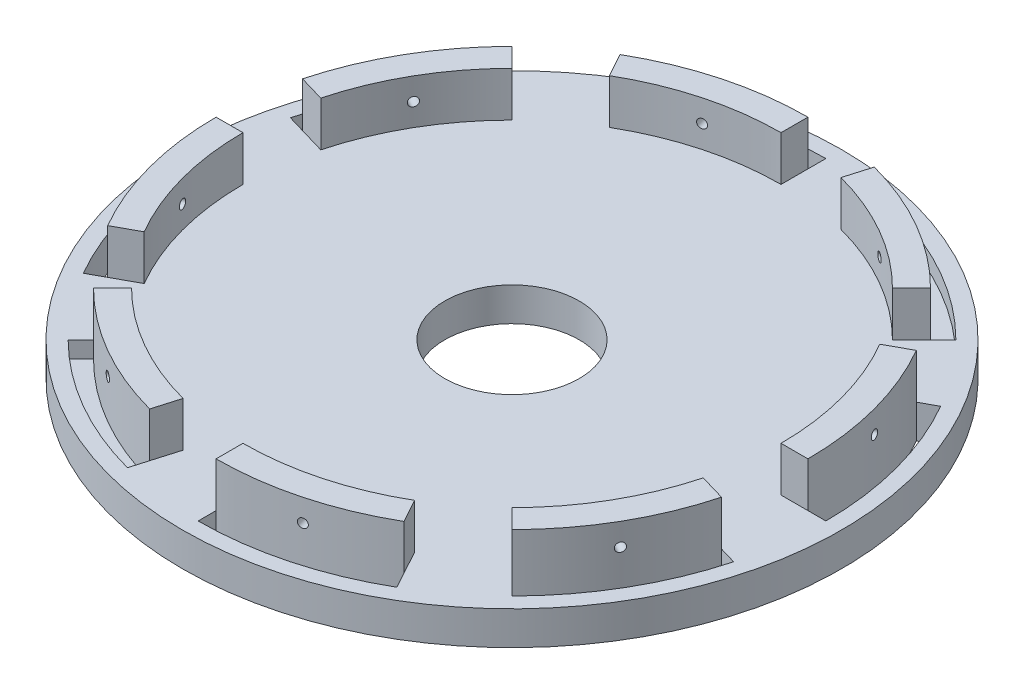
SolidWorks part; units mm, degrees
material "6061-T6 (SS)"
ref_plane "Front Plane" through (0, 0, 0) normal (0, 0, 1) x (1, 0, 0)
ref_plane "Top Plane" through (0, 0, 0) normal (0, 1, 0) x (1, 0, 0)
ref_plane "Right Plane" through (0, 0, 0) normal (1, 0, 0) x (0, 0, -1)
sketch "Sketch1" plane through (0, 0, 0) normal (0, 1, 0) x (1, 0, 0)
  circle A0 centre (0, 0) radius 93.345
  dimension "D1" = 186.69
extrude "Base" add sketch "Sketch1" along normal blind 4.7625 and the other way blind 4.7625
sketch "Sketch2" plane through (0, 4.7625, 0) normal (0, 1, 0) x (1, 0, 0)
  line L0 (0, 0) -> (0, 93.345) construction
  line L1 (-55, 0) -> (55, 0) construction
  line L2 (0, 88.9) -> (0, 83.82)
  line L3 (-41.9567, 72.5633) -> (-44.3929, 77.0226)
  line L4 (0, 0) -> (0, 93.345) construction
  arc A0 (-41.9567, 72.5633) -> (0, 83.82) centre (0, 0) cw
  arc A1 (-44.3929, 77.0226) -> (0, 88.9) centre (0, 0) cw
  circle A8 centre (0, 0) radius 93.345 construction
  dimension "D1" = 83.82
  dimension "D3" = 43.942
  dimension "D4" = 46.482
  dimension "D2" = 88.9
extrude "Bottom support holes" cut sketch "Sketch2" against normal through all
sketch "Sketch3" plane through (0, 4.7625, 0) normal (0, 1, 0) x (1, 0, 0)
  line L0 (0, 0) -> (0, 93.345) construction
  line L2 (0, 83.82) -> (0, 76.2)
  line L3 (-38.3023, 65.8739) -> (-41.9567, 72.5633)
  line L4 (-55, 0) -> (55, 0) construction
  line L7 (-44.3929, 77.0226) -> (-41.9567, 72.5633) construction
  arc A0 (-38.3023, 65.8739) -> (0, 76.2) centre (0, 0) cw
  arc A1 (-41.9567, 72.5633) -> (0, 83.82) centre (0, 0) cw
  circle A2 centre (0, 0) radius 93.345 construction
  dimension "D1" = 76.2
  dimension "D4" = 43.942
  dimension "D2" = 83.82
extrude "Bottom support guide" add sketch "Sketch3" along normal blind 12.7
ref_plane "Bottom bolt hole plane" through (-20.9784, 0, -78.1916) normal (-0.2591, 0, -0.9658) x (-0.9658, 0, 0.2591)
sketch "Sketch6" plane through (-20.9784, 0, -78.1916) normal (-0.2591, 0, -0.9658) x (-0.9658, 0, 0.2591)
  line L0 (22.9177, 4.7625) -> (-23.0366, 4.7625) construction
  line L1 (-21.7203, 4.7625) -> (-21.7203, 17.4625) construction
  circle A0 centre (-0.0033, 11.1125) radius 1.27
  dimension "D1" = 2.54
  dimension "D2" = 6.35
  dimension "D3" = 21.717
extrude "Bottom bolt hole" cut sketch "Sketch6" against normal blind 12.7 and the other way blind 12.7
sketch "Sketch8" plane through (-31.123, 4.7625, 77.2967) normal (0, 1, 0) x (1, 0, 0)
  line L0 (31.123, 77.2967) -> (-34.8819, 143.3016) construction
  line L2 (-31.7388, 140.1585) -> (-28.1467, 136.5664)
  line L3 (-49.8549, 98.9388) -> (-54.7307, 100.3694)
  line L4 (31.123, 77.2967) -> (-34.8819, 143.3016) construction
  line L5 (31.123, 77.2967) -> (31.123, 170.6417) construction
  arc A0 (-49.8549, 98.9388) -> (-28.1467, 136.5664) centre (31.123, 77.2967) cw
  arc A1 (-54.7307, 100.3694) -> (-31.7388, 140.1585) centre (31.123, 77.2967) cw
  circle A3 centre (31.123, 77.2967) radius 93.345 construction
  dimension "D1" = 83.82
  dimension "D3" = 43.942
  dimension "D4" = 46.482
  dimension "D2" = 88.9
  dimension "D5" = 45
extrude "Top support holes" cut sketch "Sketch8" against normal blind 4.7625
sketch "Sketch10" plane through (-31.123, 4.7625, 77.2967) normal (0, 1, 0) x (1, 0, 0)
  line L0 (31.123, 77.2967) -> (-34.8819, 143.3016) construction
  line L2 (-28.1467, 136.5664) -> (-22.7586, 131.1782)
  line L3 (-42.5407, 96.7928) -> (-49.8549, 98.9388)
  line L7 (-54.7307, 100.3694) -> (-49.8549, 98.9388) construction
  arc A0 (-42.5407, 96.7928) -> (-22.7586, 131.1782) centre (31.123, 77.2967) cw
  arc A1 (-49.8549, 98.9388) -> (-28.1467, 136.5664) centre (31.123, 77.2967) cw
  dimension "D1" = 76.2
  dimension "D4" = 43.942
  dimension "D2" = 83.82
extrude "Top support guide" add sketch "Sketch10" along normal blind 12.7
ref_plane "Top bolt hole plane" through (-70.1238, 0, -40.4559) normal (-0.8662, 0, -0.4997) x (-0.4997, 0, 0.8662)
sketch "Sketch12" plane through (-70.1238, 0, -40.4559) normal (-0.8662, 0, -0.4997) x (-0.4997, 0, 0.8662)
  line L0 (22.9177, 4.7625) -> (-23.0366, 4.7625) construction
  line L1 (-21.7203, 4.7625) -> (-21.7203, 17.4625) construction
  circle A0 centre (-0.0033, 11.1125) radius 1.27
  dimension "D1" = 2.54
  dimension "D2" = 6.35
  dimension "D3" = 21.717
extrude "Top bolt hole" cut sketch "Sketch12" against normal blind 12.7 and the other way blind 12.7
pattern_circular "Bottom pattern" count 4 over 360 about axis through (0, 4.7625, 0) along (0, 1, 0) of "Bottom support holes", "Bottom support guide", "Bottom bolt hole"
pattern_circular "CirPattern3" count 4 over 360 about axis through (0, 4.7625, 0) along (0, 1, 0) of "Top support holes", "Top bolt hole", "Top support guide"
sketch "Sketch13" plane through (0, 4.7625, 0) normal (0, 1, 0) x (1, 0, 0)
  circle A0 centre (0, 0) radius 19.05
  dimension "D1" = 38.1
extrude "Gimbal Hole" cut sketch "Sketch13" against normal blind 25.908
